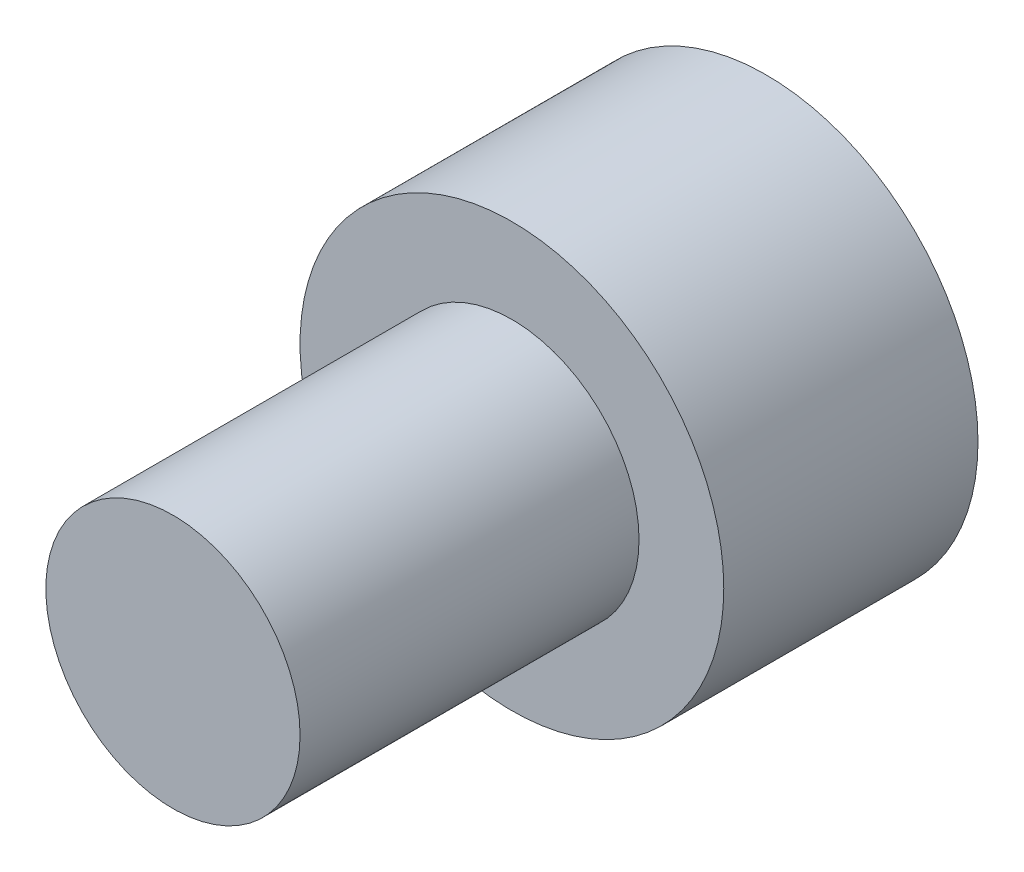
SolidWorks part; units mm, degrees
material "Liga de aço"
ref_plane "Plano frontal" through (0, 0, 0) normal (0, 0, 1) x (1, 0, 0)
ref_plane "Plano superior" through (0, 0, 0) normal (0, 1, 0) x (1, 0, 0)
ref_plane "Plano direito" through (0, 0, 0) normal (1, 0, 0) x (0, 0, -1)
sketch "Esboço1" plane through (0, 0, 0) normal (0, 0, 1) x (1, 0, 0)
  line L1 (-2.8868, 0) -> (-1.4434, -2.5)
  line L2 (-1.4434, -2.5) -> (1.4434, -2.5)
  line L3 (1.4434, -2.5) -> (2.8868, 0)
  line L4 (2.8868, 0) -> (1.4434, 2.5)
  line L5 (1.4434, 2.5) -> (-1.4434, 2.5)
  line L6 (-1.4434, 2.5) -> (-2.8868, 0)
  circle A0 centre (0, 0) radius 5
  circle A1 centre (0, 0) radius 2.5 construction
  dimension "D1" = 10
  dimension "D2" = 5
extrude "Ressalto-extrusão1" add sketch "Esboço1" along normal blind 6 contours L5 L6 L1 L2 L3 L4 | A0 L6 L5 L4 L3 L2 L1 region at (0, 0, 0) region at (-4.8586, 0, 0)
sketch "Esboço2" plane through (0, 0, 6) normal (0, 0, 1) x (1, 0, 0)
  circle A0 centre (0, 0) radius 3
  dimension "D1" = 6
extrude "Ressalto-extrusão2" add sketch "Esboço2" along normal blind 8
extrude "Corte-extrusão1" cut sketch "Esboço1<4>" along normal blind 4 contours L5 L6 L1 L2 L3 L4 region at (0, 0, 0)
sketch "Esboço1<4>" plane through (0, 0, 0) normal (0, 0, 1) x (1, 0, 0) same geometry as "Esboço1"
